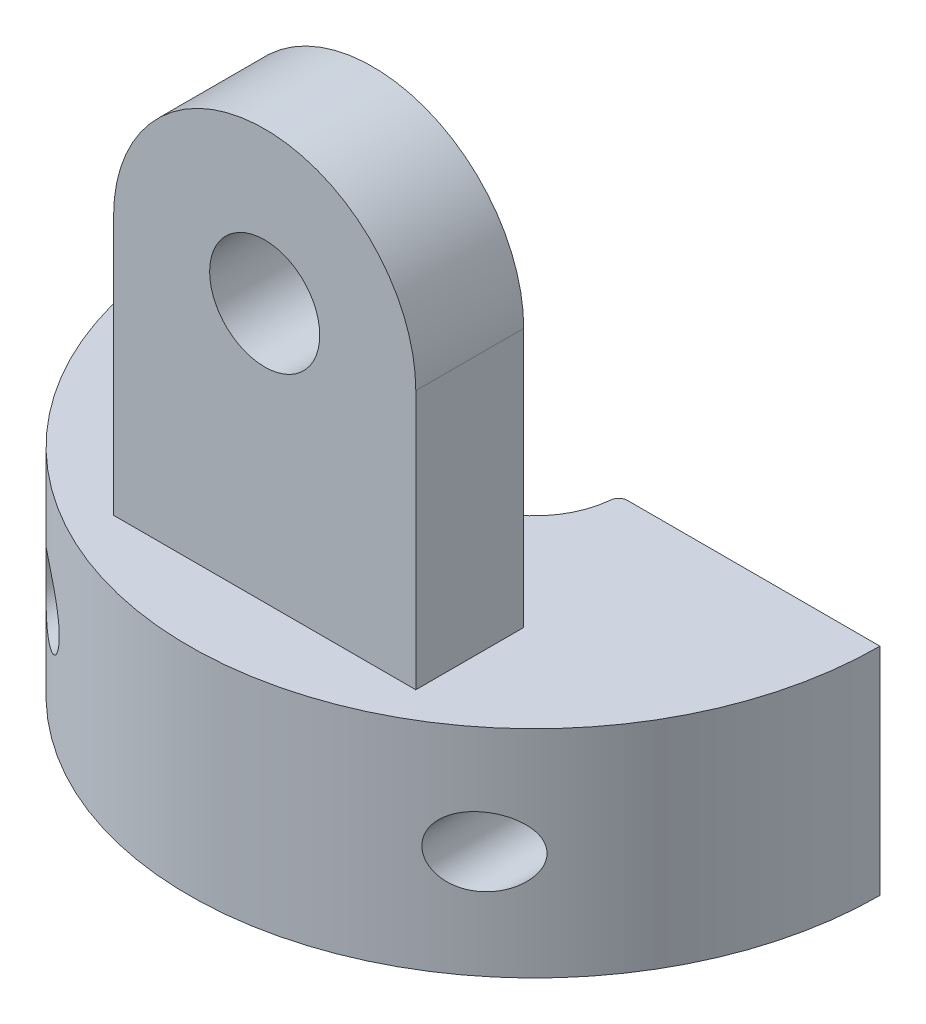
SolidWorks part; units mm, degrees
material "6061 Alloy"
ref_plane "Front Plane" through (0, 0, 0) normal (0, 0, 1) x (1, 0, 0)
ref_plane "Top Plane" through (0, 0, 0) normal (0, 1, 0) x (1, 0, 0)
ref_plane "Right Plane" through (0, 0, 0) normal (1, 0, 0) x (0, 0, -1)
sketch "Sketch1" plane through (0, 0, 0) normal (0, 1, 0) x (1, 0, 0)
  line L0 (1.96, 0) -> (8, 0)
  line L1 (-1.96, 0) -> (-8, 0)
  arc A0 (-8, 0) -> (8, 0) centre (0, 0) ccw
  arc A1 (1.96, 0) -> (-1.96, 0) centre (0, 0) cw
  dimension "D1" = 1.96
  dimension "D2" = 8
extrude "Boss-Extrude1" add sketch "Sketch1" along normal mid plane 5 contours L0 A0 L1 A1
sketch "Sketch2" plane through (0, 2.5, 0) normal (0, 1, 0) x (1, 0, 0)
  line L0 (3.5, -3.75) -> (-3.5, -3.75)
  line L1 (-3.5, -3.75) -> (-3.5, -6.25)
  line L2 (3.5, -6.25) -> (3.5, -3.75)
  line L3 (3.5, -6.25) -> (-3.5, -6.25)
  arc A0 (-3.5, -6.25) -> (3.5, -6.25) centre (0, 0) ccw construction
  arc A1 (-8, 0) -> (8, 0) centre (0, 0) ccw construction
  dimension "D1" = 2.5
  dimension "D2" = 3.75
  dimension "D3" = 7
extrude "Boss-Extrude2" add sketch "Sketch2" along normal blind 9.5 contours L2 L0 L1 L3
sketch "Sketch3" plane through (0, 0, 3.75) normal (0, 0, -1) x (-1, 0, 0)
  line L0 (3.5, 12) -> (3.5, 2.5) construction
  line L1 (-3.5, 8.5) -> (-3.5, 14.8864)
  line L2 (-3.5, 14.8864) -> (0, 16.8092)
  line L3 (0, 16.8092) -> (3.5, 14.5)
  line L4 (3.5, 14.5) -> (3.5, 8.5)
  line L6 (-3.5, 12) -> (3.5, 12) construction
  line L7 (-3.5, 12) -> (-3.5, 2.5) construction
  arc A0 (3.5, 8.5) -> (-3.5, 8.5) centre (0, 8.5) ccw
extrude "Cut-Extrude1" cut sketch "Sketch3" against normal blind 9.5 contours L3 L4 A0 L1 L2
sketch "Sketch4" plane through (0, 0, 3.75) normal (0, 0, -1) x (-1, 0, 0)
  circle A0 centre (0, 8.5) radius 1.275
  dimension "D1" = 2.55
extrude "Cut-Extrude2" cut sketch "Sketch4" against normal blind 9.5
sketch "Sketch9" plane through (0, 0, 0) normal (0, 0, 1) x (1, 0, 0)
  line L0 (0, 0.5) -> (-3, 2.5)
  line L1 (-1.96, 2.5) -> (-8, 2.5) construction
  line L2 (-3, 2.5) -> (0, 2.5)
  line L3 (0, 2.5) -> (0, 0.5)
  dimension "D1" = 3
  dimension "D2" = 2
hole_wizard "M2x0.4 Tapped Hole1" positions "Sketch10" profile "Sketch11" tap size "M2x0.4" standard "ANSI Metric" end condition through all
sketch "Sketch10" plane through (0, 0, 0) normal (0, 0, -1) x (-1, 0, 0)
  point P0 (-5, 0)
  point P2 (5, 0)
  dimension "D1" = 5
  dimension "D2" = 5
sketch "Sketch11" plane through (5, 0, 0) normal (1, 0, 0) x (0, 1, 0)
  line L0 (0, 0) -> (0, 8)
  line L1 (0, 8) -> (0.8, 8)
  line L2 (0.8, 8) -> (0.8, 0)
  line L5 (0.8, 0) -> (0, 0)
  line L11 (0, -6.35) -> (0, 107.95) construction
  dimension "Thru Tap Drill Dia." = 1.6
  dimension "Thru Tap Drill Depth" = 8
cosmetic thread "Hole Thread1" parameters "D2"=2
cosmetic thread "Hole Thread2" parameters "D2"=2
fillet "Fillet1" radius 0.2 2 edges at (-1.96, 0, 0) (1.96, 0, 0)
